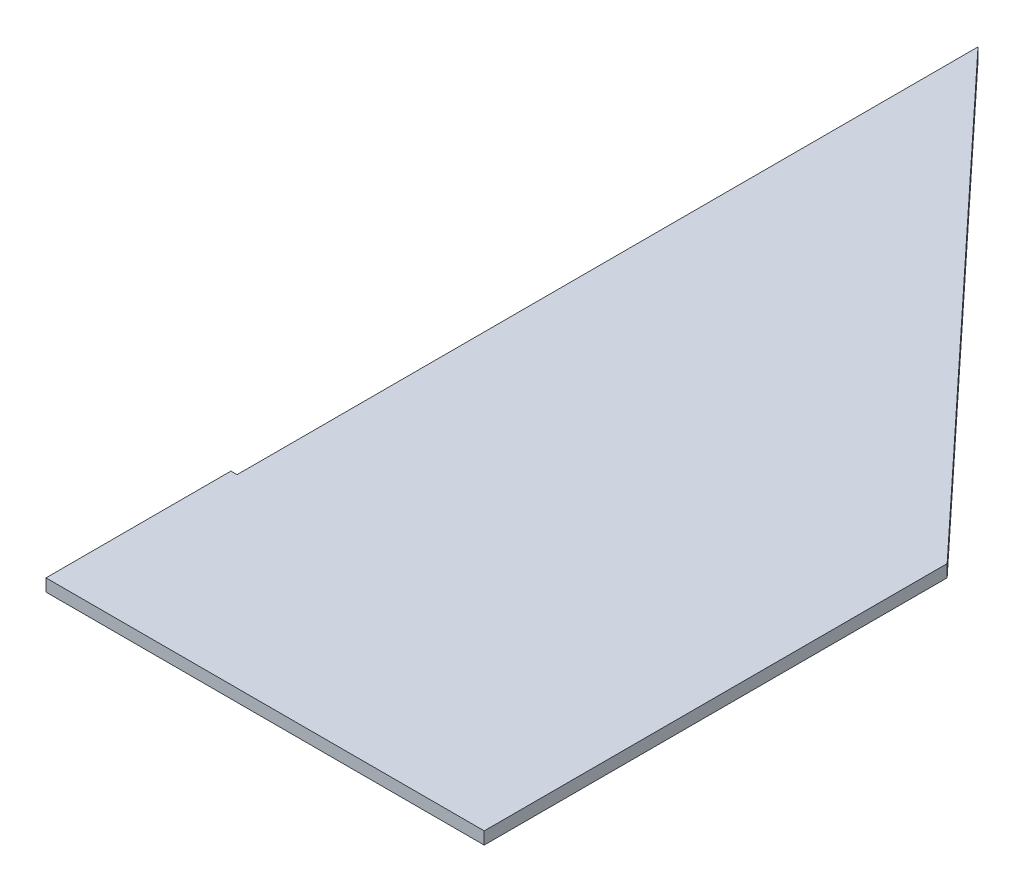
SolidWorks part; units mm, degrees
material "Fibra di Carbonio"
ref_plane "Piano frontale" through (0, 0, 0) normal (0, 0, 1) x (1, 0, 0)
ref_plane "Piano superiore" through (0, 0, 0) normal (0, 1, 0) x (1, 0, 0)
ref_plane "Piano destro" through (0, 0, 0) normal (1, 0, 0) x (0, 0, -1)
sketch "Forma aletta" plane through (0, 0, 0) normal (0, 1, 0) x (1, 0, 0)
  line L0 (0, 0) -> (0, 300) construction
  line L1 (0, 300) -> (0, 59.93)
  line L2 (0, 0) -> (140, 0)
  line L3 (140, 0) -> (140, 150)
  line L4 (140, 150) -> (0, 300)
  line L5 (0, 0) -> (-2, 0)
  line L6 (-2, 0) -> (-2, 59.93)
  line L7 (-2, 59.93) -> (0, 59.93)
  line L8 (-146, 59.93) -> (0, 59.93) construction
  line L9 (-146, 59.93) -> (0, 59.93) construction
  dimension "D1" = 300
  dimension "D2" = 2
  dimension "D3" = 205.1828
  dimension "D6" = 140
extrude "Estrusione-Estrusione1" add sketch "Forma aletta" along normal blind 2 and the other way blind 2
